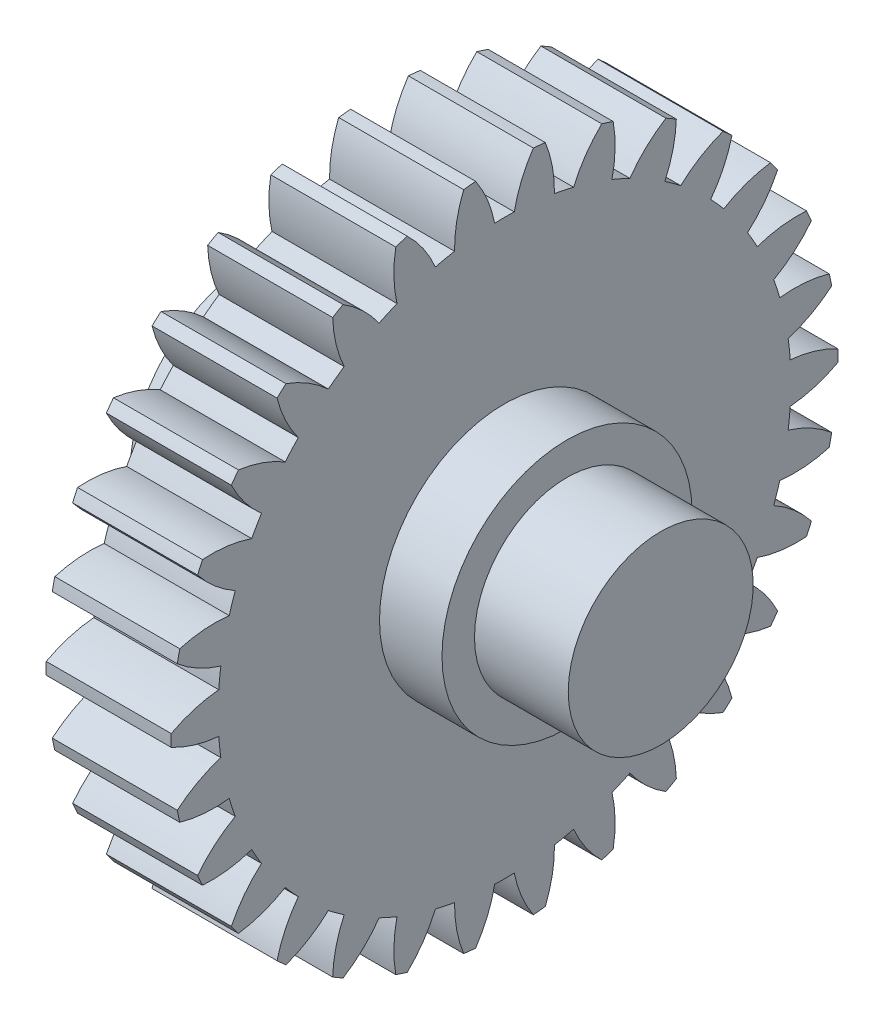
SolidWorks part; units mm, degrees
ref_plane "Plane1" through (0, 0, 0) normal (0, 0, 1) x (1, 0, 0)
ref_plane "Plane2" through (0, 0, 0) normal (0, 1, 0) x (1, 0, 0)
ref_plane "Plane3" through (0, 0, 0) normal (1, 0, 0) x (0, 0, -1)
other "Configuration Table"
sketch "HoldingSke" plane through (0, 0, 0) normal (0, 1, 0) x (1, 0, 0)
  line L0 (0, 0) -> (263.9645, -152.4)
  line L1 (-15, 0) -> (100, 0) construction
  line L2 (0, 0) -> (-2.1039, 2.3779)
  line L3 (0, 0) -> (-11.863, 4.5341)
  line L4 (0, 0) -> (7.479, 4.318)
  line L5 (0, 0) -> (-47.5972, -17.7524)
  line L6 (0, 0) -> (-10.5278, -7.1032)
  line L7 (-2.1039, 2.3779) -> (8.8311, 51.9885)
  line L8 (-76.2, 54.61) -> (-54.9402, 54.61)
  line L9 (-71.009, 38.7566) -> (-53.1078, 45.2721)
  line L10 (-76.2, 71.12) -> (104.1128, 71.12)
  line L11 (0, 0) -> (-12.7, 0)
  line L12 (-76.2, 101.6) -> (-76.1147, 101.6)
  line L13 (24.9733, 27.94) -> (52.9518, 28.4284)
  line L14 (24.9733, 27.94) -> (24.9746, 27.94)
  line L15 (24.9733, 27.94) -> (100.4006, 29.5858)
  circle A0 centre (0, 0) radius 9.525
  circle A1 centre (0, 0) radius 29.1029
  circle A2 centre (0, 0) radius 38.1
  circle A3 centre (0, 0) radius 9.525
  dimension "MHD" = 58.2058
  dimension "Hub_dia" = 76.2
  dimension "Bore" = 19.05
  dimension "MBD" = 19.05
  dimension "Num_teeth" = 30
  dimension "Pitch" = 304.8
  dimension "Overall_len" = 50.8
  dimension "Show_teeth" = 30
  dimension "Thickness" = 12.7
  dimension "OAL" = 50.8014
  dimension "T_dim" = 21.2598
  dimension "Ap" = 20
  dimension "H" = 19.05
  dimension "Pitch_radius" = 180.3128
  dimension "Width" = 12.7
  dimension "Backlash" = 0.0853
  dimension "Addendum_fac" = 1
  dimension "Dedendum_fac" = 1.25
  dimension "Clearance_fac" = 0.25
  dimension "Dedendum_add" = 0.0013
sketch "BasProSke" plane through (0, 0, 0) normal (0, 1, 0) x (1, 0, 0)
  line L0 (-10, 0) -> (60, 0) construction
  line L1 (0, 0) -> (0, 33.8667)
  line L2 (0, 0) -> (12.7, 0)
  line L3 (12.7, 0) -> (12.7, 33.8667)
  line L4 (12.7, 33.8667) -> (0, 33.8667)
  dimension "Thickness" = 12.7
  dimension "Diameter" = 67.7333
revolve "Base-Revolve" add sketch "BasProSke" angle 360 about L0
sketch "TooCutSke" plane through (0, 0, 0) normal (1, 0, 0) x (0, 0, -1)
  line L1 (0, 0) -> (0, 107) construction
  line L2 (0, 0) -> (-1.811, 31.6983) construction
  line L3 (0, 0) -> (-6.63, 63.0805) construction
  line L4 (-1.811, 31.6983) -> (-3.315, 31.5402) construction
  arc A0 (0.9953, 29.0859) -> (-0.9953, 29.0859) centre (0, 0) ccw
  arc A1 (2.9488, 33.7635) -> (-2.9488, 33.7635) centre (0, 0) ccw
  circle A2 centre (0, 0) radius 31.75 construction
  circle A3 centre (0, 0) radius 29.8352 construction
  arc A4 (-0.9953, 29.0859) -> (-2.9488, 33.7635) centre (-13.4553, 26.6289) ccw
  arc A5 (2.9488, 33.7635) -> (0.9953, 29.0859) centre (13.4553, 26.6289) ccw
  dimension "Root_dia" = 58.2058
  dimension "Overcut_dia" = 67.7841
  dimension "Pitch_dia" = 63.5
  dimension "Base_dia" = 59.6705
  dimension "Flank_rad" = 12.7
  dimension "Half_ang" = 6
  dimension "Half_CT" = 1.5123
extrude "ToothCut" cut sketch "TooCutSke" along normal through all
fillet "Breaks" [suppressed] radius 0.0423 tangent propagation no
fillet "RootFillets" [suppressed] radius 0.5304
pattern_circular "TeethCuts" count 30 every 12 about axis through (-10, 0, 0) along (1, 0, 0) of "ToothCut", "RootFillets", "Breaks"
sketch "HubNeaOneSke" plane through (0, 0, 0) normal (-1, 0, 0) x (0, 0, 1)
  circle A0 centre (0, 0) radius 29.1029
  dimension "Diameter" = 58.2058
extrude "HubNearOne" [suppressed] add sketch "HubNeaOneSke" along normal blind 38.1014
sketch "HubNeaBotSke" plane through (0, 0, 0) normal (-1, 0, 0) x (0, 0, 1)
  circle A0 centre (0, 0) radius 29.1029
  dimension "Diameter" = 58.2058
extrude "HubNearBoth" [suppressed] add sketch "HubNeaBotSke" along normal blind 19.0507
ref_plane "FarPln" through (12.7, 0, 0) normal (1, 0, 0) x (0, 0, -1)
sketch "HubFarSke" plane through (12.7, 0, 0) normal (1, 0, 0) x (0, 0, -1)
  circle A0 centre (0, 0) radius 29.1029
  dimension "Diameter" = 58.2058
extrude "HubFar" [suppressed] add sketch "HubFarSke" along normal blind 19.0507
sketch "Sketch1" plane through (0, 0, 0) normal (-1, 0, 0) x (0, 0, 1)
  circle A0 centre (0, 0) radius 12.7
  circle A1 centre (0, 0) radius 4.953
  dimension "D1" = 9.906
  dimension "D2" = 25.4
extrude "Boss-Extrude2" add sketch "Sketch1" along normal blind 12.7
sketch "Sketch3" plane through (0, 0, 0) normal (0, 1, 0) x (1, 0, 0)
  line L0 (0, 0.9953) -> (0, -0.9953) construction
  line L2 (-12.7, 0) -> (0, 0) construction
  circle A0 centre (-6.35, 0) radius 3.302
  dimension "D1" = 6.604
  dimension "D2" = 6.35
extrude "Cut-Extrude1" cut sketch "Sketch3" along normal through all
sketch "Sketch4" plane through (0, 0, 0) normal (0, 1, 0) x (1, 0, 0)
  line L1 (-3.527, 4.8895) -> (-9.173, 4.8895)
  line L2 (-9.173, 4.8895) -> (-11.9959, 0)
  line L3 (-11.9959, 0) -> (-9.173, -4.8895)
  line L4 (-9.173, -4.8895) -> (-3.527, -4.8895)
  line L5 (-3.527, -4.8895) -> (-0.7041, 0)
  line L6 (-0.7041, 0) -> (-3.527, 4.8895)
  line L7 (0, 12.7) -> (-12.7, 12.7) construction
  circle A0 centre (-6.35, 0) radius 4.8895 construction
  dimension "D1" = 9.779
extrude "Cut-Extrude2" cut sketch "Sketch4" along normal blind 8.255 contours L3 L4 L5 L6 L1 L2
sketch "Sketch5" plane through (12.7, 0, 0) normal (1, 0, 0) x (0, 0, -1)
  circle A0 centre (0, 0) radius 12.7
  dimension "D1" = 25.4
extrude "Boss-Extrude3" add sketch "Sketch5" along normal blind 6.35
sketch "Sketch6" plane through (19.05, 0, 0) normal (1, 0, 0) x (0, 0, -1)
  circle A0 centre (0, 0) radius 9.398
  dimension "D1" = 18.796
extrude "Boss-Extrude4" add sketch "Sketch6" along normal blind 9.525
equation "' \"Pitch@HoldingSke\" = 4"
equation "' \"Num_teeth@HoldingSke\" = 12"
equation "' \"Ap@HoldingSke\" =  20"
equation "' \"Ap@HoldingSke\" = 20"
equation "' \"Width@HoldingSke\" = 0.5"
equation "' \"Hub_dia@HoldingSke\"= 1"
equation "' \"Hub_dia@HoldingSke\" = 1"
equation "' \"Overall_len@HoldingSke\" = 1.0"
equation "' \"Bore@HoldingSke\" = 0.75"
equation "' \"T_dim@HoldingSke\" = 0.85"
equation "' \"Width@KeySke\" = 0.25"
equation "' \"Show_teeth@HoldingSke\" = 13"
equation "' \"Backlash@HoldingSke\" = 0.009"
equation "' \"Addendum_fac@HoldingSke\" = 1.0"
equation "' \"Dedendum_fac@HoldingSke\" = 1.25"
equation "' \"Dedendum_add@HoldingSke\" = 0.00005"
equation "' \"Clearance_fac@HoldingSke\" = 0.25"
equation "' \"Pitch@HoldingSke\" = 0.5"
equation "' \"Num_teeth@HoldingSke\" = 23"
equation "' \"Show_teeth@HoldingSke\" = 23"
equation "' \"Backlash@HoldingSke\" = 0.0375"
equation "\"Overcut_dia@TooCutSke\" = (\"Num_teeth@HoldingSke\" + 2 * \"Addendum_fac@HoldingSke\") / \"Pitch@HoldingSke\" + 0.002"
equation "\"Pitch_dia@TooCutSke\" = \"Num_teeth@HoldingSke\" / \"Pitch@HoldingSke\""
equation "\"Base_dia@TooCutSke\" = \"Num_teeth@HoldingSke\" / \"Pitch@HoldingSke\" * cos((\"Ap@HoldingSke\"  * 3.14159265 / 180))"
equation "\"Root_dia@TooCutSke\" = (\"Num_teeth@HoldingSke\" + 2) / \"Pitch@HoldingSke\" - 2 * (\"Addendum_fac@HoldingSke\" + \"Dedendum_fac@HoldingSke\") / \"Pitch@HoldingSke\" - \"Dedendum_add@HoldingSke\" * 2"
equation "\"Half_ang@TooCutSke\" = 180 / \"Num_teeth@HoldingSke\""
equation "\"Half_CT@TooCutSke\" = \"Num_teeth@HoldingSke\" / \"Pitch@HoldingSke\" * sin((3.14159265 / 2 / \"Num_teeth@HoldingSke\")) / 2 - 7 * \"Backlash@HoldingSke\" / 4"
equation "\"Flank_rad@TooCutSke\" = \"Num_teeth@HoldingSke\" / \"Pitch@HoldingSke\" / 5"
equation "\"Radius@RootFillets\" = \"Clearance_fac@HoldingSke\" / \"Pitch@HoldingSke\" + \"Dedendum_add@HoldingSke\""
equation "\"Break_rad@Breaks\" = 0.02 / \"Pitch@HoldingSke\""
equation "\"Thickness@HoldingSke\" = \"Width@HoldingSke\""
equation "\"OAL@HoldingSke\" = \"Thickness@HoldingSke\""
equation "\"MHD@HoldingSke\" = (\"Num_teeth@HoldingSke\" + 2) / \"Pitch@HoldingSke\" - 2 * (\"Addendum_fac@HoldingSke\" + \"Dedendum_fac@HoldingSke\")  / \"Pitch@HoldingSke\" - \"Dedendum_add@HoldingSke\" * 2"
equation "\"MBD@HoldingSke\" = (\"Num_teeth@HoldingSke\" + 2) / \"Pitch@HoldingSke\" - 2 * (\"Addendum_fac@HoldingSke\" + \"Dedendum_fac@HoldingSke\")  / \"Pitch@HoldingSke\" - \"Dedendum_add@HoldingSke\" * 2 - 0.002"
equation "\"MHD@HoldingSke\" = ((sgn( \"MHD@HoldingSke\" - \"Hub_dia@HoldingSke\" )-1)*( \"MHD@HoldingSke\" - \"Hub_dia@HoldingSke\" ))/-2+ \"Hub_dia@HoldingSke\""
equation "\"MBD@HoldingSke\" = ((sgn( \"MBD@HoldingSke\" - \"Bore@HoldingSke\" )-1)*( \"MBD@HoldingSke\" - \"Bore@HoldingSke\" ))/-2+ \"Bore@HoldingSke\""
equation "\"OAL@HoldingSke\" = ((sgn( \"OAL@HoldingSke\" - \"Overall_len@HoldingSke\" )+1)*( \"OAL@HoldingSke\" - \"Overall_len@HoldingSke\" ))/2 + \"Overall_len@HoldingSke\" + 0.000002"
equation "\"Num_teeth@TeethCuts\" = int( \"Show_teeth@HoldingSke\" ) + 1"
equation "\"Num_teeth@TeethCuts\" = ((sgn( \"Num_teeth@TeethCuts\" - \"Num_teeth@HoldingSke\" )-1)*( \"Num_teeth@TeethCuts\" - \"Num_teeth@HoldingSke\" ))/-2+ \"Num_teeth@HoldingSke\""
equation "\"Num_teeth@TeethCuts\" = ((sgn( \"Num_teeth@TeethCuts\" - 2.0)+1)*( \"Num_teeth@TeethCuts\" - 2.0))/2 +2.0"
equation "\"Angle@TeethCuts\" = 360.0 / \"Num_teeth@HoldingSke\""
equation "\"Diameter@BasProSke\" = (\"Num_teeth@HoldingSke\" + 2 * \"Addendum_fac@HoldingSke\") / \"Pitch@HoldingSke\""
equation "\"Thickness@BasProSke\"  = \"Thickness@HoldingSke\""
equation "' \"Fillet_rad@BasProSke\" =  \"Thickness@HoldingSke\" * 0.05"
equation "' \"Fillet_rad@BasProSke\" = \"Thickness@HoldingSke\" * 0.05"
equation "\"MHD@HoldingSke\" = ((sgn( \"MHD@HoldingSke\" - \"Root_dia@TooCutSke\" )-1)*( \"MHD@HoldingSke\" - \"Root_dia@TooCutSke\" ))/-2+ \"Root_dia@TooCutSke\""
equation "\"Diameter@HubNeaOneSke\" = \"MHD@HoldingSke\""
equation "\"Length@HubNearOne\" = \"OAL@HoldingSke\" - \"Thickness@BasProSke\""
equation "\"Diameter@HubNeaBotSke\" = \"MHD@HoldingSke\""
equation "\"Length@HubNearBoth\" = ( \"OAL@HoldingSke\" - \"Thickness@BasProSke\" ) / 2.0"
equation "\"Thickness@FarPln\" = \"Thickness@BasProSke\""
equation "\"Diameter@HubFarSke\" = \"MHD@HoldingSke\""
equation "\"Length@HubFar\" = ( \"OAL@HoldingSke\" - \"Thickness@BasProSke\" ) / 2.0"
equation "\"Diameter@BorSke\" = \"MBD@HoldingSke\""
equation "\"D1\"= \"OAL@HoldingSke\" * 2.0"
equation "\"Offset@KeySke\" = \"T_dim@HoldingSke\" - \"MBD@HoldingSke\" / 2.0"
